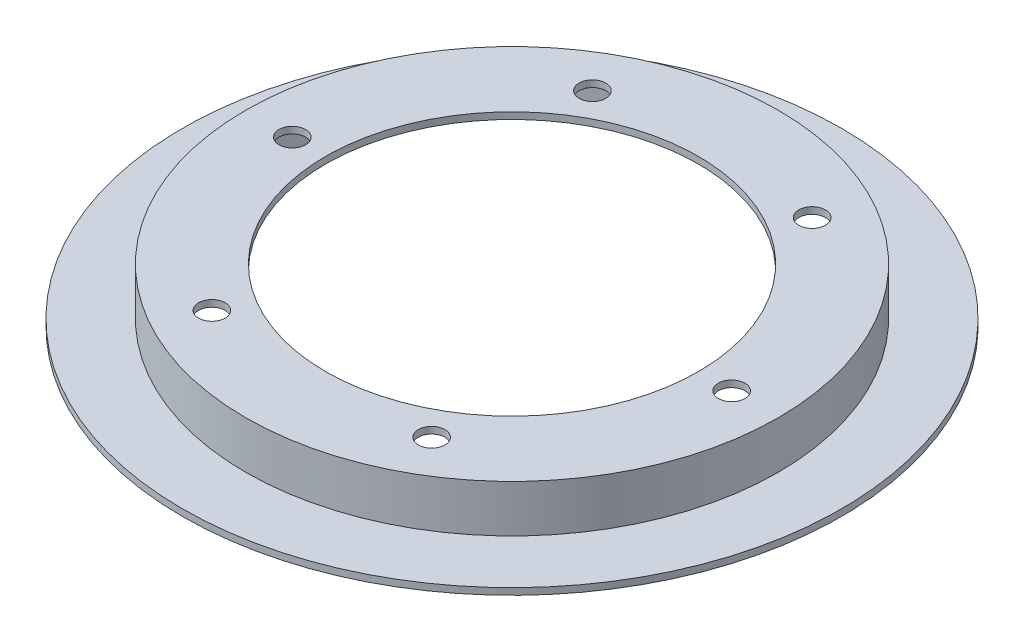
SolidWorks part; units mm, degrees
ref_plane "前视基准面" through (0, 0, 0) normal (0, 0, 1) x (1, 0, 0)
ref_plane "上视基准面" through (0, 0, 0) normal (0, 1, 0) x (1, 0, 0)
ref_plane "右视基准面" through (0, 0, 0) normal (1, 0, 0) x (0, 0, -1)
sketch "草图1" plane through (0, 0, 0) normal (0, 1, 0) x (1, 0, 0)
  line L0 (0, 0) -> (33, 0) construction
  circle A0 centre (0, 0) radius 28
  circle A1 centre (0, 0) radius 49.5
  circle A2 centre (33, 0) radius 2
  circle A3 centre (16.5, -28.5788) radius 2
  circle A4 centre (-16.5, -28.5788) radius 2
  circle A5 centre (-33, 0) radius 2
  circle A6 centre (-16.5, 28.5788) radius 2
  circle A7 centre (16.5, 28.5788) radius 2
  circle A8 centre (0, 0) radius 40
  circle A9 centre (0, 0) radius 39
  dimension "D1" = 56
  dimension "D2" = 99
  dimension "D5" = 4
  dimension "D6" = 80
  dimension "D7" = 78
  dimension "D4" = 33
  dimension "D3" = 6
extrude "凸台-拉伸1" add sketch "草图1" against normal blind 1 contours A9 A7 A6 A5 A4 A3 A0 A2 | A8 A9 region at (-39.8869, 0, 0) region at (-37.8969, 0, 0)
extrude "凸台-拉伸2" add sketch "草图1<3>" against normal blind 7.1 contours A8 A9 region at (-39.8869, 0, 0)
sketch "草图1<3>" plane through (0, 0, 0) normal (0, 1, 0) x (1, 0, 0) same geometry as "草图1"
sketch "草图2" plane through (0, -7.1, 0) normal (0, -1, 0) x (1, 0, 0)
  circle A0 centre (0, 0) radius 39 construction
  circle A1 centre (0, 0) radius 39
  circle A2 centre (0, 0) radius 49.5
  dimension "D1" = 99
extrude "凸台-拉伸3" add sketch "草图2" along normal blind 1
sketch "草图4" plane through (0, 0, 0) normal (1, 0, 0) x (0, 0, -1)
  line L0 (39, -8.1) -> (30, -1)
  line L1 (-28, -1) -> (28, -1) construction
  line L2 (40, -7.1) -> (40, 0) construction
  dimension "D1" = 10
rib "筋1" sketch "草图4" sketch "草图4" thickness 3 extrusion direction parallel to sketch draft on no parameters "D1"=3
pattern_circular "阵列(圆周)1" count 6 over 360 about axis through (0, -7.1, 0) along (0, 1, 0) of "筋1"
